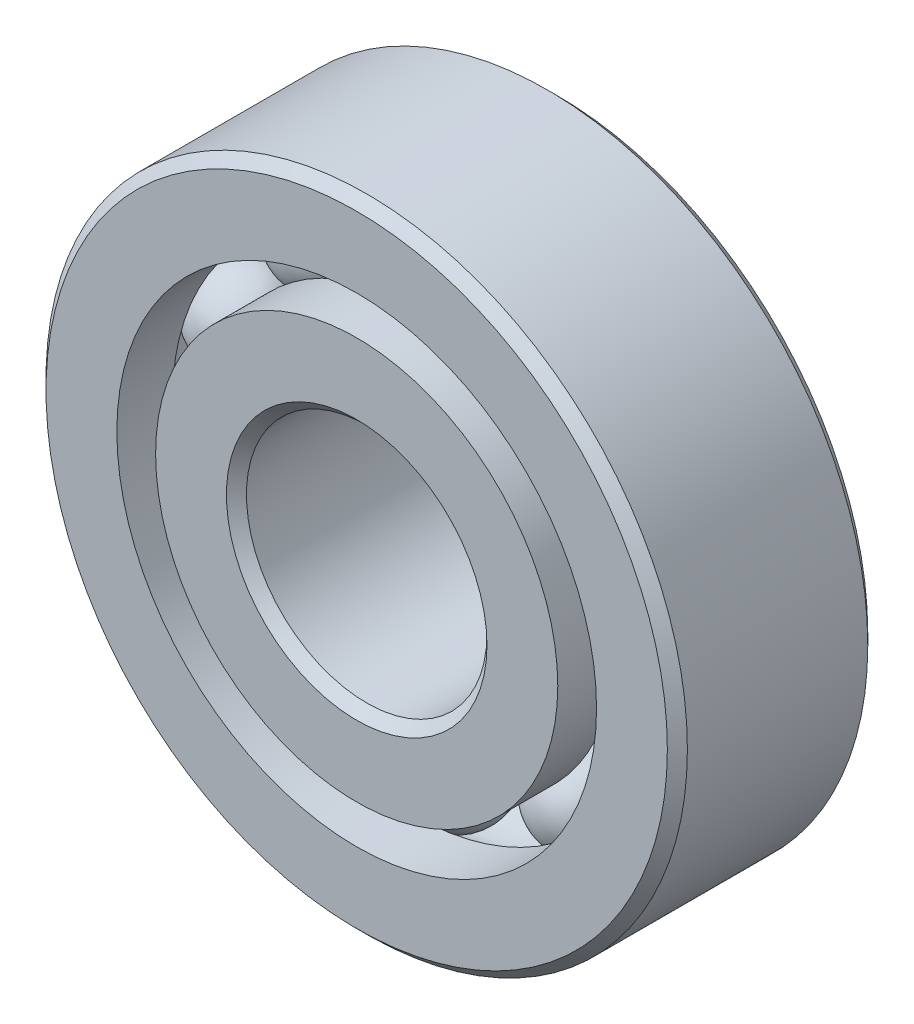
SolidWorks part; units mm, degrees
ref_plane "Front Plane" through (0, 0, 0) normal (0, 0, 1) x (1, 0, 0)
ref_plane "Top Plane" through (0, 0, 0) normal (0, 1, 0) x (1, 0, 0)
ref_plane "Right Plane" through (0, 0, 0) normal (1, 0, 0) x (0, 0, -1)
sketch "Sketch1" plane through (0, 0, 0) normal (1, 0, 0) x (0, 0, -1)
  line L0 (-1.9844, 0) -> (1.9844, 0) construction
  line L1 (0, 6.35) -> (0, -6.35) construction
  line L2 (1.7859, 6.35) -> (-1.7859, 6.35)
  line L3 (-1.7859, 6.35) -> (-1.9844, 6.1516)
  line L4 (-1.9844, 6.1516) -> (-1.9844, 4.7494)
  line L5 (-1.9844, 4.7494) -> (-0.8819, 4.7494)
  line L6 (1.9844, 4.7494) -> (0.8819, 4.7494)
  line L7 (1.9844, 6.1516) -> (1.9844, 4.7494)
  line L8 (1.7859, 6.35) -> (1.9844, 6.1516)
  line L9 (0, 6.35) -> (0, 4.3656) construction
  line L10 (0, 4.3656) -> (0, 2.3813) construction
  arc A0 (-0.8819, 4.7494) -> (0.8819, 4.7494) centre (0, 4.3656) cw
  point P14 (0, 2.3813)
  dimension "Width" = 3.9688
  dimension "OD" = 12.7
  dimension "D1" = 45
  dimension "D2" = 0.1984
  dimension "Shaft Dia" = 4.7625
  dimension "D3" = 1.7639
  dimension "D4" = 0.3838
revolve "Revolve1" add sketch "Sketch1" angle 360 about L0
sketch "Sketch3" plane through (0, 0, 0) normal (1, 0, 0) x (0, 0, -1)
  line L0 (-1.9844, 3.9818) -> (-0.8819, 3.9818)
  line L1 (0, 6.35) -> (0, -6.35) construction
  line L2 (-1.9844, 6.1516) -> (-1.9844, 4.7494) construction
  line L3 (-1.9844, 3.9818) -> (-1.9844, 2.5797)
  line L4 (-1.7859, 6.35) -> (-1.9844, 6.1516) construction
  line L5 (-1.9844, 2.5797) -> (-1.7859, 2.3813)
  line L6 (-1.7859, 2.3813) -> (1.7859, 2.3813)
  line L7 (1.7859, 6.35) -> (1.7859, -6.35) construction
  line L8 (1.7859, 2.3813) -> (1.9844, 2.5797)
  line L9 (1.9844, -6.1516) -> (1.9844, 6.1516) construction
  line L10 (1.9844, 2.5797) -> (1.9844, 3.9818)
  line L11 (1.9844, 3.9818) -> (0.8819, 3.9818)
  line L13 (1.7859, 6.35) -> (1.9844, 6.1516) construction
  arc A0 (0.8819, 4.7494) -> (-0.8819, 4.7494) centre (0, 4.3656) ccw construction
  arc A1 (0.8819, 3.9818) -> (-0.8819, 3.9818) centre (0, 4.3656) cw
revolve "Revolve3" add sketch "Sketch3" angle 360 about L0
sketch "Sketch4" plane through (0, 0, 0) normal (1, 0, 0) x (0, 0, -1)
  line L0 (-0.9618, 4.3656) -> (0.9618, 4.3656)
  arc A2 (-0.9618, 4.3656) -> (0.9618, 4.3656) centre (0, 4.3656) cw
  arc A3 (0.8819, 4.7494) -> (-0.8819, 4.7494) centre (0, 4.3656) ccw construction
revolve "Revolve4" add sketch "Sketch4" angle 360 about L0
ref_axis "Axis1" through (0, 0, -1.9844) along (0, 0, 1)
pattern_circular "CirPattern1" count 10 every 36 about axis through (0, 0, -1.9844) along (0, 0, 1) of bodies 104
sketch "Sketch5" plane through (0, 0, 0) normal (1, 0, 0) x (0, 0, -1)
  line L0 (-1.9844, 4.7494) -> (-0.8819, 4.7494) construction
  line L1 (-1.8852, 4.7494) -> (-0.9618, 4.7494)
  line L2 (-1.8852, 4.7494) -> (-1.8852, 3.9818)
  line L3 (-1.8852, 3.9818) -> (-0.9618, 3.9818)
  line L4 (-0.9618, 4.7494) -> (-0.9618, 3.9818)
  line L5 (-1.9844, 3.9818) -> (-0.8819, 3.9818) construction
  line L6 (1.9844, 4.7494) -> (0.8819, 4.7494) construction
  line L7 (1.8852, 4.7494) -> (0.9618, 4.7494)
  line L8 (1.8852, 4.7494) -> (1.8852, 3.9818)
  line L9 (1.8852, 3.9818) -> (0.9618, 3.9818)
  line L10 (0.9618, 4.7494) -> (0.9618, 3.9818)
  line L11 (1.9844, 3.9818) -> (0.8819, 3.9818) construction
  line L12 (-1.7859, 6.35) -> (-1.9844, 6.1516) construction
  point P18 (-1.8852, 6.2508)
revolve "Revolve5" [suppressed] add sketch "Sketch5" angle 360 about L0
equation "\"D2@Sketch1\" = \"Width@Sketch1\"*.05"
equation "\"D3@Sketch1\" = \"Width@Sketch1\"/2.25"
equation "\"D4@Sketch1\" = (((\"OD@Sketch1\"-\"Width@Sketch1\")/2)/3.25)/3.5"
equation "\"D2@CirPattern1\" = 360/\"Balls@CirPattern1\""
